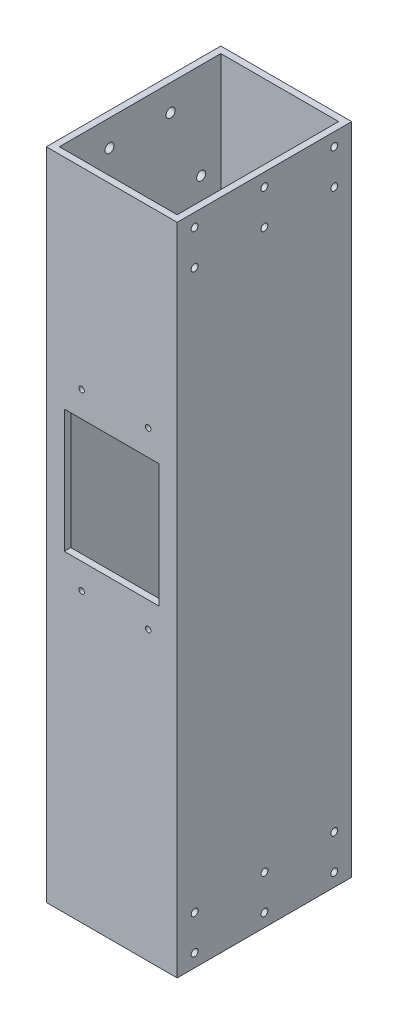
SolidWorks part; units mm, degrees
other "gp1_link"
other "drill guide"
material "6061-T6 (SS)"
ref_plane "Front Plane" through (0, 0, 0) normal (0, 0, 1) x (1, 0, 0)
ref_plane "Top Plane" through (0, 0, 0) normal (0, 1, 0) x (1, 0, 0)
ref_plane "Right Plane" through (0, 0, 0) normal (1, 0, 0) x (0, 0, -1)
sketch "Sketch1" plane through (0, 0, 0) normal (0, 1, 0) x (1, 0, 0)
  line L0 (3, 3) -> (3, 77)
  line L1 (0, 0) -> (60, 0)
  line L2 (0, 0) -> (0, 80)
  line L3 (0, 80) -> (60, 80)
  line L4 (60, 0) -> (60, 80)
  line L5 (3, 77) -> (57, 77)
  line L6 (57, 3) -> (57, 77)
  line L7 (3, 3) -> (57, 3)
  dimension "D1" = 80
  dimension "D2" = 60
  dimension "D3" = 3
extrude "Boss-Extrude1" add sketch "Sketch1" along normal blind 300
sketch "Sketch2" plane through (0, 0, 0) normal (0, 0, 1) x (1, 0, 0)
  line L0 (30, 300) -> (30, 200) construction
  line L1 (8.25, 200) -> (51.75, 200)
  line L2 (8.25, 200) -> (8.25, 143.5)
  line L3 (8.25, 143.5) -> (51.75, 143.5)
  line L4 (51.75, 200) -> (51.75, 143.5)
  line L5 (0, 300) -> (60, 300) construction
  dimension "D1" = 43.5
  dimension "D2" = 100
  dimension "D3" = 56.5
extrude "Cut-Extrude1" cut sketch "Sketch2" against normal up to next
sketch "Sketch3" plane through (0, 0, 0) normal (0, 0, 1) x (1, 0, 0)
  line L3 (15.4832, 200) -> (8.25, 200) construction
  line L4 (60, 300) -> (60, 0) construction
  line L7 (46.7, 131.75) -> (16.2, 131.75) construction
  line L9 (16.2, 211.75) -> (46.7, 211.75) construction
  line L14 (46.7, 131.75) -> (46.7, 211.75) construction
  line L16 (46.7, 171.75) -> (51.75, 171.75) construction
  line L17 (51.75, 143.5) -> (51.75, 200) construction
  point P0 (16.2, 211.75)
  point P11 (46.7, 211.75)
  point P12 (46.7, 131.75)
  point P13 (16.2, 131.75)
  dimension "D1" = 13.3
  dimension "D2" = 30.5
  dimension "D6" = 80
  dimension "D3" = 2
  dimension "D4" = 2
hole_wizard "Tap Drill for M3 Tap1" positions "Sketch3" profile "Sketch5" hole size "M3" standard "DIN" end condition up to next
sketch "Sketch5" plane through (16.2, 211.75, 0) normal (1, 0, 0) x (0, -1, 0)
  line L0 (0, 0) -> (0, 3)
  line L1 (0, 3) -> (1.25, 3)
  line L2 (1.25, 3) -> (1.25, 0)
  line L5 (1.25, 0) -> (0, 0)
  line L11 (0, -6.35) -> (0, 107.95) construction
  dimension "Thru Hole Dia." = 2.5
  dimension "Thru Hole Depth" = 3
sketch "Sketch8" plane through (0, 0, 0) normal (-1, 0, 0) x (0, 0, 1)
  line L0 (-80, 0) -> (0, 0) construction
  point P0 (-8, 6)
  point P8 (-40, 6)
  point P9 (-72, 6)
  point P10 (-40, 22)
  point P11 (-72, 22)
  point P12 (-8, 22)
  dimension "D3" = 6
  dimension "D1" = 3
  dimension "D2" = 2
hole_wizard "Tap Drill for M3 Helicoil2" positions "Sketch8" profile "Sketch7" hole size "M3x0.5" standard "DIN" end condition through all
sketch "Sketch7" plane through (0, 6, -8) normal (0, 1, 0) x (0, 0, 1)
  line L0 (0, 0) -> (0, 60)
  line L1 (0, 60) -> (1.575, 60)
  line L2 (1.575, 60) -> (1.575, 0)
  line L5 (1.575, 0) -> (0, 0)
  line L11 (0, -6.35) -> (0, 107.95) construction
  dimension "Thru Hole Dia." = 3.15
  dimension "Thru Hole Depth" = 60
sketch "Sketch11" plane through (60, 0, 0) normal (1, 0, 0) x (0, 0, -1)
  line L3 (40, 300) -> (40, 248.3318) construction
  line L4 (0, 300) -> (80, 300) construction
  point P45 (8, 294)
  point P50 (40, 294)
  point P51 (72, 294)
  point P52 (40, 278)
  point P53 (72, 278)
  point P54 (8, 278)
  dimension "D1" = 3
  dimension "D3" = 6
  dimension "D2" = 2
hole_wizard "Tap Drill for M3 Helicoil2" positions "Sketch11" profile "Sketch10" hole size "M3x0.5" standard "DIN" end condition up to next
sketch "Sketch10" plane through (60, 294, -8) normal (0, 1, 0) x (0, 0, -1)
  line L0 (0, 0) -> (0, 3)
  line L1 (0, 3) -> (1.575, 3)
  line L2 (1.575, 3) -> (1.575, 0)
  line L5 (1.575, 0) -> (0, 0)
  line L11 (0, -6.35) -> (0, 107.95) construction
  dimension "Thru Hole Dia." = 3.15
  dimension "Thru Hole Depth" = 3
sketch "Sketch14" plane through (0, 0, 0) normal (-1, 0, 0) x (0, 0, 1)
  point P0 (-68, 256)
  point P3 (-12, 256)
  point P6 (-26, 288)
  point P9 (-54, 288)
hole_wizard "Tap Drill for M5 Tap1" positions "Sketch14" profile "Sketch13" hole size "M5" standard "DIN" end condition up to next
sketch "Sketch13" plane through (0, 256, -68) normal (0, 1, 0) x (0, 0, 1)
  line L0 (0, 0) -> (0, 3)
  line L1 (0, 3) -> (2.1, 3)
  line L2 (2.1, 3) -> (2.1, 0)
  line L5 (2.1, 0) -> (0, 0)
  line L11 (0, -6.35) -> (0, 107.95) construction
  dimension "Thru Hole Dia." = 4.2
  dimension "Thru Hole Depth" = 3
sketch "Sketch15" plane through (0, 0, 0) normal (-1, 0, 0) x (0, 0, 1)
  line L0 (-80, 244) -> (-84, 244)
  line L1 (-80, 300) -> (-80, 0) construction
  line L2 (-84, 244) -> (-84, 304)
  line L3 (-84, 304) -> (4, 304)
  line L4 (4, 304) -> (4, 244)
  line L5 (4, 244) -> (0, 244)
  line L6 (0, 300) -> (0, 0) construction
  line L7 (0, 244) -> (0, 300)
  line L8 (0, 300) -> (-80, 300)
  line L9 (-80, 300) -> (0, 300) construction
  line L10 (-80, 300) -> (-80, 244)
  dimension "D1" = 4
  dimension "D2" = 4
  dimension "D3" = 60
extrude "Boss-Extrude2" add sketch "Sketch15" against normal blind 6 separate body
sketch "Sketch16" plane through (0, 0, 0) normal (-1, 0, 0) x (0, 0, 1)
  line L0 (-40, 304) -> (-40, 296) construction
  line L1 (-84, 304) -> (4, 304)
  line L2 (-84, 304) -> (-84, 244)
  line L3 (-84, 244) -> (4, 244)
  line L4 (4, 304) -> (4, 244)
  line L5 (-77.5, 282) -> (-2.5, 282)
  line L6 (-77.5, 282) -> (-77.5, 262)
  line L7 (-77.5, 262) -> (-2.5, 262)
  line L8 (-2.5, 282) -> (-2.5, 262)
  line L9 (-47.5, 282) -> (-32.5, 282)
  line L10 (-47.5, 282) -> (-47.5, 296)
  line L11 (-47.5, 296) -> (-32.5, 296)
  line L12 (-32.5, 282) -> (-32.5, 296)
  line L13 (-40, 296) -> (-40, 262) construction
  line L14 (-40, 262) -> (-40, 252) construction
  line L15 (-60, 262) -> (-20, 262)
  line L16 (-60, 262) -> (-60, 252)
  line L17 (-60, 252) -> (-20, 252)
  line L18 (-20, 262) -> (-20, 252)
  circle A0 centre (-54, 288) radius 2.9
  circle A1 centre (-26, 288) radius 2.9
  circle A2 centre (-12, 256) radius 2.9
  circle A3 centre (-68, 256) radius 2.9
  point P18 (-40, 304)
  line M22 (-80, 244) -> (-80, 300)
  line M23 (-80, 300) -> (0, 300)
  line M24 (0, 300) -> (0, 244)
  line M25 (0, 244) -> (4, 244)
  line M26 (4, 244) -> (4, 304)
  line M27 (4, 304) -> (-84, 304)
  line M28 (-84, 304) -> (-84, 244)
  line M29 (-84, 244) -> (-80, 244)
  dimension "D6" = 5.8
  dimension "D7" = 40
  dimension "D1" = 75
  dimension "D2" = 15
  dimension "D3" = 20
  dimension "D4" = 8
  dimension "D5" = 14
  dimension "D8" = 10
extrude "Boss-Extrude3" add sketch "Sketch16" along normal blind 6 contours M29 M22 M23 M24 M25 M26 M27 M28 | L3 A3 A2 A1 A0 L7 L18 L17 L16 L6 L5 L10 L11 L12 L8 M22 M24 M23 region at (0, 302.9349, -40) region at (0, 272, -79.0235)
fillet "Fillet1" radius 2 12 edges at (-3, 262, -2.5) (-3, 282, -2.5) (-3, 282, -32.5) (-3, 296, -47.5) (-3, 282, -47.5) (-3, 282, -77.5) (-3, 262, -77.5) (-3, 262, -60) (-3, 252, -60) (-3, 252, -20) (-3, 262, -20) (-3, 296, -32.5)
delete or keep bodies "Body-Delete/Keep 1" type delete bodies bodies 109
